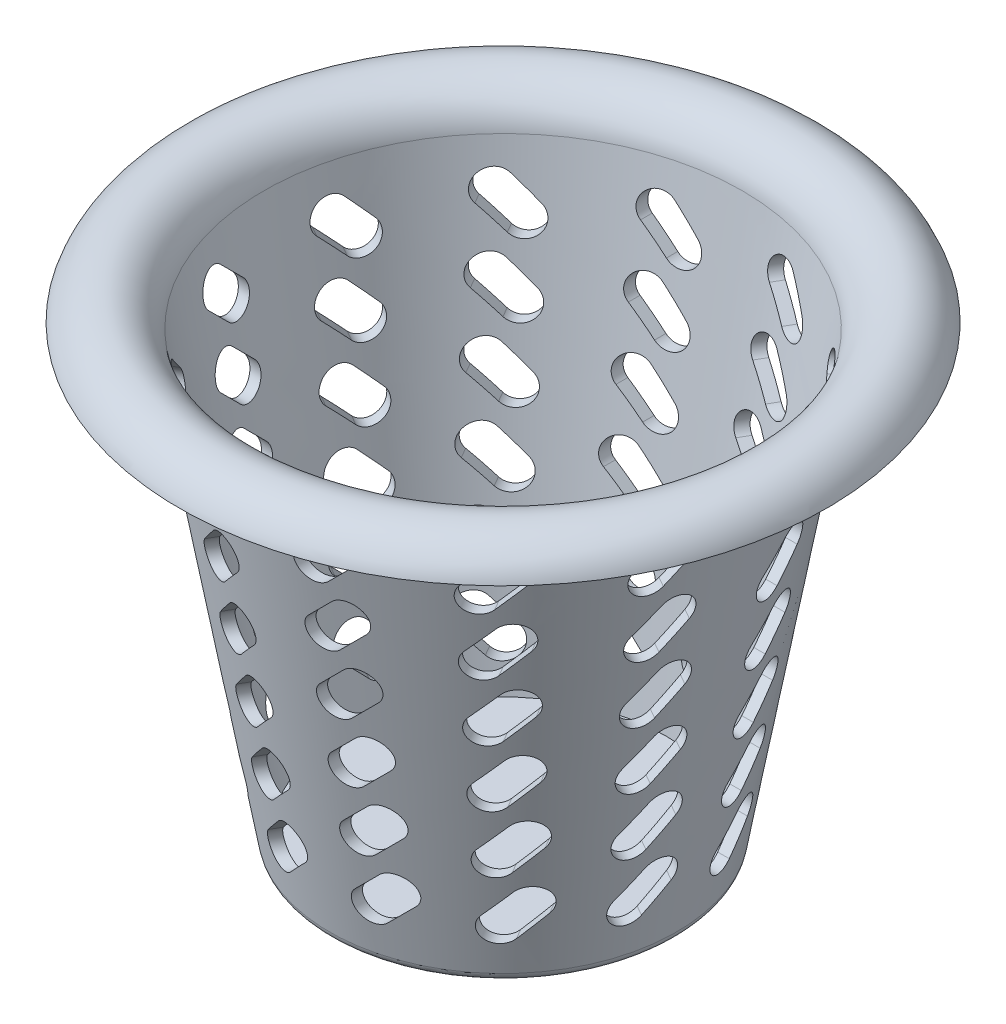
SolidWorks part; units mm, degrees
ref_plane "Front Plane" through (0, 0, 0) normal (0, 0, 1) x (1, 0, 0)
ref_plane "Top Plane" through (0, 0, 0) normal (0, 1, 0) x (1, 0, 0)
ref_plane "Right Plane" through (0, 0, 0) normal (1, 0, 0) x (0, 0, -1)
sketch "Sketch1" plane through (0, 0, 0) normal (0, 0, 1) x (1, 0, 0)
  line L0 (0, 0) -> (150, 0)
  line L1 (150, 0) -> (220.5308, 400)
  line L2 (0, 0) -> (0, 216.4975) construction
  arc A0 (220.5308, 400) -> (297.9563, 405.4427) centre (259.9231, 393.0541) cw
  dimension "D3" = 40
  dimension "D1" = 150
  dimension "D2" = 400
  dimension "D4" = 100
revolve "Revolve-Thin1" add sketch "Sketch1" angle 360 about L2
fillet "Fillet1" radius 10 1 edges at (0, -10, -158.391)
sketch "Sketch2" plane through (0, 0, 0) normal (0, 0, 1) x (1, 0, 0)
  line L0 (0, 455.0182) -> (0, 0) construction
  line L1 (0, 0) -> (-123.6396, 123.6396) construction
  line L2 (-61.8198, 61.8198) -> (-40.6066, 40.6066) construction
  line L3 (-51.2132, 72.4264) -> (-30, 51.2132)
  line L4 (-72.4264, 51.2132) -> (-51.2132, 30)
  arc A0 (-51.2132, 72.4264) -> (-72.4264, 51.2132) centre (-61.8198, 61.8198) ccw
  arc A1 (-51.2132, 30) -> (-30, 51.2132) centre (-40.6066, 40.6066) ccw
  point P6 (-51.2132, 51.2132)
  point P11 (-30, 30)
  point P12 (-72.4264, 72.4264)
  point P15 (0, 3.1308)
  dimension "D1" = 45
  dimension "D2" = 30
  dimension "D3" = 60
  dimension "D4" = 30
extrude "Cut-Extrude1" cut sketch "Sketch2" against normal through all
pattern_linear "LPattern1" count 6 spacing 60 along (0, 1, 0) of "Cut-Extrude1"
pattern_circular "CirPattern1" count 12 over 360 about axis through (0, 0, 0) along (0, 1, 0) of "LPattern1", "Cut-Extrude1"
